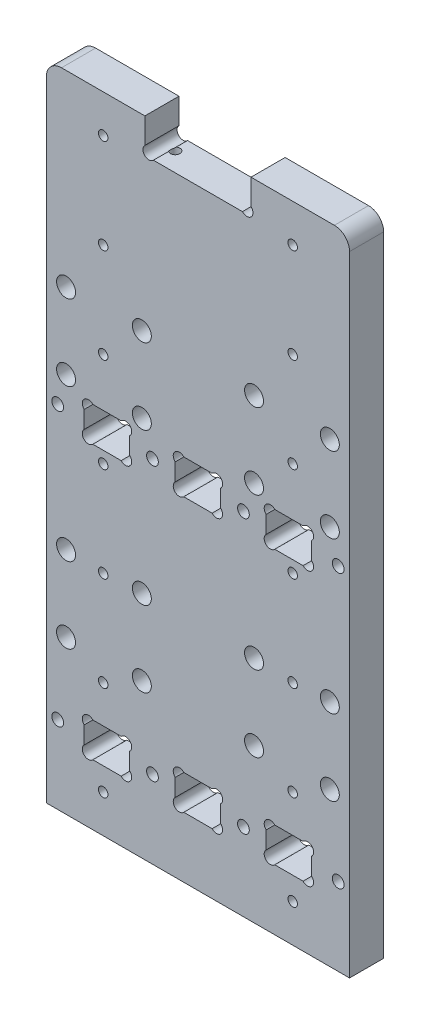
SolidWorks part; units mm, degrees
ref_plane "Front" through (0, 0, 0) normal (0, 0, 1) x (1, 0, 0)
ref_plane "Top" through (0, 0, 0) normal (0, 1, 0) x (1, 0, 0)
ref_plane "Right" through (0, 0, 0) normal (1, 0, 0) x (0, 0, -1)
sketch "Esquisse1" plane through (0, 0, 0) normal (0, 0, 1) x (1, 0, 0)
  line L1 (0, 0) -> (80, 0)
  line L2 (0, 0) -> (0, 170)
  line L3 (0, 170) -> (80, 170)
  line L4 (80, 0) -> (80, 170)
  dimension "D1" = 80
  dimension "D2" = 170
extrude "Boss.-Extru.1" add sketch "Esquisse1" along normal blind 9
sketch "Esquisse2" plane through (0, 0, 9) normal (0, 0, 1) x (1, 0, 0)
  line L0 (40, 0) -> (40, 170) construction
  line L1 (0, 0) -> (80, 0) construction
  line L2 (80, 170) -> (0, 170) construction
  line L3 (15, 10) -> (15, 35) construction
  circle A0 centre (15, 10) radius 1.25
  circle A1 centre (65, 10) radius 1.25
  circle A2 centre (15, 35) radius 1.25
  circle A3 centre (65, 35) radius 1.25
  circle A4 centre (15, 60) radius 1.25
  circle A5 centre (65, 60) radius 1.25
  circle A6 centre (15, 85) radius 1.25
  circle A7 centre (65, 85) radius 1.25
  circle A8 centre (15, 110) radius 1.25
  circle A9 centre (65, 110) radius 1.25
  circle A10 centre (15, 135) radius 1.25
  circle A11 centre (65, 135) radius 1.25
  circle A12 centre (15, 160) radius 1.25
  circle A13 centre (65, 160) radius 1.25
  circle A14 centre (15, 185) radius 1.25
  circle A15 centre (65, 185) radius 1.25
  dimension "D2" = 2.5
  dimension "D1" = 50
  dimension "D3" = 10
  dimension "D5" = 25
  dimension "D4" = 8
extrude "Enlèv. mat.-Extru.1" cut sketch "Esquisse2" against normal through all
sketch "Esquisse4" plane through (0, 0, 9) normal (0, 0, 1) x (1, 0, 0)
  line L0 (40, 170) -> (40, 161) construction
  line L1 (80, 170) -> (0, 170) construction
  line L2 (54, 161) -> (26, 161)
  line L3 (26, 161) -> (26, 170)
  line L4 (26, 170) -> (54, 170)
  line L5 (54, 161) -> (54, 170)
  dimension "D1" = 28
  dimension "D2" = 9
extrude "Enlèv. mat.-Extru.3" cut sketch "Esquisse4" against normal through all
sketch "Esquisse5" plane through (0, 161, 0) normal (0, 1, 0) x (1, 0, 0)
  line L0 (29, 0) -> (29, -4) construction
  line L1 (26, 0) -> (54, 0) construction
  line L2 (40, 0) -> (40, -4.3659) construction
  circle A0 centre (29, -4) radius 1.25
  circle A1 centre (51, -4) radius 1.25
  dimension "D1" = 2.5
  dimension "D2" = 4
  dimension "D3" = 22
extrude "Enlèv. mat.-Extru.4" cut sketch "Esquisse5" against normal blind 10
sketch "Esquisse6" plane through (0, 0, 9) normal (0, 0, 1) x (1, 0, 0)
  line L0 (74.8, 120.5) -> (74.8, 80.5) construction
  line L1 (40, 161) -> (40, 0) construction
  line L2 (26, 161) -> (54, 161) construction
  line L3 (0, 0) -> (80, 0) construction
  line L5 (74.8, 80.5) -> (40, 80.5) construction
  line L6 (5.2, 120.5) -> (5.2, 80.5) construction
  line L7 (74.8, 120.5) -> (64.8, 120.5) construction
  line L8 (64.8, 120.5) -> (64.8, 124.5729) construction
  circle A0 centre (74.8, 120.5) radius 2.5
  circle A1 centre (74.8, 60.5) radius 2.5
  circle A2 centre (74.8, 100.5) radius 2.5
  circle A3 centre (74.8, 40.5) radius 2.5
  circle A4 centre (5.2, 40.5) radius 2.5
  circle A5 centre (5.2, 100.5) radius 2.5
  circle A6 centre (5.2, 60.5) radius 2.5
  circle A7 centre (5.2, 120.5) radius 2.5
  circle A8 centre (54.8, 100.5) radius 2.5
  circle A9 centre (54.8, 120.5) radius 2.5
  circle A10 centre (54.8, 40.5) radius 2.5
  circle A11 centre (54.8, 60.5) radius 2.5
  circle A12 centre (25.2, 60.5) radius 2.5
  circle A13 centre (25.2, 40.5) radius 2.5
  circle A14 centre (25.2, 120.5) radius 2.5
  circle A15 centre (25.2, 100.5) radius 2.5
  dimension "D3" = 5
  dimension "D5" = 20
  dimension "D1" = 34.8
  dimension "D2" = 20
  dimension "D4" = 20
extrude "Enlèv. mat.-Extru.5" cut sketch "Esquisse6" against normal through all
fillet "Congé1" radius 4 2 edges at (80, 170, 4.5) (0, 170, 4.5)
sketch "Esquisse7" plane through (0, 0, 9) normal (0, 0, 1) x (1, 0, 0)
  line L0 (40, 0) -> (40, 161) construction
  line L1 (10, 25.1) -> (22, 25.1)
  line L2 (10, 25.1) -> (10, 16)
  line L3 (10, 16) -> (22, 16)
  line L4 (22, 25.1) -> (22, 16)
  line L5 (0, 0) -> (80, 0) construction
  line L6 (26, 161) -> (54, 161) construction
  line L7 (46, 25.1) -> (34, 25.1)
  line L8 (34, 25.1) -> (34, 16)
  line L9 (34, 16) -> (46, 16)
  line L10 (46, 25.1) -> (46, 16)
  line L11 (58, 25.1) -> (58, 16)
  line L12 (70, 16) -> (58, 16)
  line L13 (70, 25.1) -> (70, 16)
  line L14 (70, 25.1) -> (58, 25.1)
  line L15 (16, 25.1) -> (16, 88.1) construction
  line L16 (16, 56.6) -> (27.6071, 56.6) construction
  line L17 (70, 88.1) -> (58, 88.1)
  line L18 (70, 88.1) -> (70, 97.2)
  line L19 (70, 97.2) -> (58, 97.2)
  line L20 (58, 88.1) -> (58, 97.2)
  line L21 (46, 88.1) -> (46, 97.2)
  line L22 (34, 97.2) -> (46, 97.2)
  line L23 (34, 88.1) -> (34, 97.2)
  line L24 (46, 88.1) -> (34, 88.1)
  line L25 (22, 88.1) -> (22, 97.2)
  line L26 (10, 97.2) -> (22, 97.2)
  line L27 (10, 88.1) -> (10, 97.2)
  line L28 (10, 88.1) -> (22, 88.1)
  point P14 (34, 20.55)
  point P16 (40, 16)
  point P17 (40, 25.1)
  point P37 (40, 88.1)
  point P38 (40, 97.2)
  dimension "D1" = 12
  dimension "D2" = 12
  dimension "D3" = 12
  dimension "D4" = 16
  dimension "D5" = 9.1
  dimension "D6" = 63
extrude "Enlèv. mat.-Extru.6" cut sketch "Esquisse7" against normal through all
sketch "Esquisse8" plane through (0, 0, 9) normal (0, 0, 1) x (1, 0, 0)
  line L0 (10, 16) -> (10, 15.9) construction
  line L1 (10, 16) -> (9.9, 16) construction
  line L2 (10, 16) -> (11.0803, 17.0803) construction
  line L3 (10, 16) -> (22, 16) construction
  line L4 (16, 16) -> (16, 25.1) construction
  line L5 (22, 25.1) -> (10, 25.1) construction
  line L6 (16, 20.55) -> (10, 20.55) construction
  line L7 (10, 25.1) -> (10, 16) construction
  line L8 (10, 25.1) -> (11.0803, 24.0197) construction
  line L9 (10, 25.1) -> (9.9, 25.1) construction
  line L10 (10, 25.1) -> (10, 25.2) construction
  line L11 (22, 25.1) -> (22, 25.2) construction
  line L12 (22, 25.1) -> (22.1, 25.1) construction
  line L13 (22, 25.1) -> (20.9197, 24.0197) construction
  line L14 (22, 16) -> (20.9197, 17.0803) construction
  line L15 (22, 16) -> (22.1, 16) construction
  line L16 (22, 16) -> (22, 15.9) construction
  line L17 (22, 20.55) -> (34, 20.55) construction
  line L18 (22, 16) -> (22, 25.1) construction
  line L19 (34, 25.1) -> (34, 16) construction
  line L20 (40, 16) -> (40, 25.1) construction
  line L21 (34, 16) -> (46, 16) construction
  line L22 (46, 25.1) -> (34, 25.1) construction
  line L23 (28, 20.55) -> (28, 29.7274) construction
  line L24 (34, 16) -> (34, 15.9) construction
  line L25 (34, 16) -> (33.9, 16) construction
  line L26 (34, 16) -> (35.0803, 17.0803) construction
  line L27 (34, 25.1) -> (35.0803, 24.0197) construction
  line L28 (34, 25.1) -> (33.9, 25.1) construction
  line L29 (34, 25.1) -> (34, 25.2) construction
  line L30 (46, 25.1) -> (46, 25.2) construction
  line L31 (46, 25.1) -> (46.1, 25.1) construction
  line L32 (46, 25.1) -> (44.9197, 24.0197) construction
  line L33 (46, 16) -> (44.9197, 17.0803) construction
  line L34 (46, 16) -> (46.1, 16) construction
  line L35 (46, 16) -> (46, 15.9) construction
  line L36 (58, 20.55) -> (46, 20.55) construction
  line L37 (58, 16) -> (58, 15.9) construction
  line L38 (58, 16) -> (57.9, 16) construction
  line L39 (58, 16) -> (59.0803, 17.0803) construction
  line L40 (58, 25.1) -> (59.0803, 24.0197) construction
  line L41 (58, 25.1) -> (57.9, 25.1) construction
  line L42 (58, 25.1) -> (58, 25.2) construction
  line L43 (70, 25.1) -> (70, 25.2) construction
  line L44 (70, 25.1) -> (70.1, 25.1) construction
  line L45 (70, 25.1) -> (68.9197, 24.0197) construction
  line L46 (64, 20.55) -> (70, 20.55) construction
  line L47 (64, 16) -> (64, 25.1) construction
  line L48 (70, 16) -> (68.9197, 17.0803) construction
  line L49 (70, 16) -> (70.1, 16) construction
  line L50 (70, 16) -> (70, 15.9) construction
  line L51 (16, 25.1) -> (16, 88.1) construction
  line L52 (10, 88.1) -> (22, 88.1) construction
  line L53 (16, 56.6) -> (40, 56.6) construction
  line L54 (70, 97.2) -> (70, 97.3) construction
  line L55 (70, 97.2) -> (70.1, 97.2) construction
  line L56 (70, 97.2) -> (68.9197, 96.1197) construction
  line L57 (64, 97.2) -> (64, 88.1) construction
  line L58 (64, 92.65) -> (70, 92.65) construction
  line L59 (70, 88.1) -> (68.9197, 89.1803) construction
  line L60 (70, 88.1) -> (70.1, 88.1) construction
  line L61 (70, 88.1) -> (70, 88) construction
  line L62 (58, 88.1) -> (58, 88) construction
  line L63 (58, 88.1) -> (57.9, 88.1) construction
  line L64 (58, 88.1) -> (59.0803, 89.1803) construction
  line L65 (58, 97.2) -> (59.0803, 96.1197) construction
  line L66 (58, 97.2) -> (57.9, 97.2) construction
  line L67 (58, 97.2) -> (58, 97.3) construction
  line L68 (58, 92.65) -> (46, 92.65) construction
  line L69 (46, 97.2) -> (46, 97.3) construction
  line L70 (46, 97.2) -> (46.1, 97.2) construction
  line L71 (46, 97.2) -> (44.9197, 96.1197) construction
  line L72 (46, 88.1) -> (44.9197, 89.1803) construction
  line L73 (46, 88.1) -> (46.1, 88.1) construction
  line L74 (46, 88.1) -> (46, 88) construction
  line L75 (34, 88.1) -> (34, 88) construction
  line L76 (34, 88.1) -> (33.9, 88.1) construction
  line L77 (34, 88.1) -> (35.0803, 89.1803) construction
  line L78 (34, 97.2) -> (35.0803, 96.1197) construction
  line L79 (34, 97.2) -> (33.9, 97.2) construction
  line L80 (34, 97.2) -> (34, 97.3) construction
  line L81 (40, 97.2) -> (40, 88.1) construction
  line L82 (22, 92.65) -> (34, 92.65) construction
  line L83 (22, 97.2) -> (22, 97.3) construction
  line L84 (22, 97.2) -> (22.1, 97.2) construction
  line L86 (22, 88.1) -> (20.9197, 89.1803) construction
  line L87 (22, 88.1) -> (22.1, 88.1) construction
  line L88 (22, 88.1) -> (22, 88) construction
  line L89 (10, 88.1) -> (10, 88) construction
  line L90 (10, 88.1) -> (9.9, 88.1) construction
  line L91 (10, 88.1) -> (11.0803, 89.1803) construction
  line L92 (16, 92.65) -> (10, 92.65) construction
  line L93 (16, 97.2) -> (16, 88.1) construction
  line L94 (10, 97.2) -> (11.0803, 96.1197) construction
  line L95 (10, 97.2) -> (9.9, 97.2) construction
  line L96 (10, 97.2) -> (10, 97.3) construction
  line L97 (26, 161) -> (26, 160.9) construction
  line L98 (26, 161) -> (25.9, 161) construction
  line L99 (40, 161) -> (40, 171.5112) construction
  line L100 (26, 161) -> (54, 161) construction
  line L101 (54, 161) -> (54.1, 161) construction
  line L102 (54, 161) -> (54, 160.9) construction
  circle A0 centre (11.0803, 17.0803) radius 1.6
  circle A1 centre (11.0803, 24.0197) radius 1.6
  circle A2 centre (20.9197, 24.0197) radius 1.6
  circle A3 centre (20.9197, 17.0803) radius 1.6
  circle A4 centre (35.0803, 17.0803) radius 1.6
  circle A5 centre (35.0803, 24.0197) radius 1.6
  circle A6 centre (44.9197, 24.0197) radius 1.6
  circle A7 centre (44.9197, 17.0803) radius 1.6
  circle A8 centre (59.0803, 17.0803) radius 1.6
  circle A9 centre (59.0803, 24.0197) radius 1.6
  circle A10 centre (68.9197, 24.0197) radius 1.6
  circle A11 centre (68.9197, 17.0803) radius 1.6
  circle A12 centre (68.9197, 96.1197) radius 1.6
  circle A13 centre (68.9197, 89.1803) radius 1.6
  circle A14 centre (59.0803, 89.1803) radius 1.6
  circle A15 centre (59.0803, 96.1197) radius 1.6
  circle A16 centre (44.9197, 96.1197) radius 1.6
  circle A17 centre (44.9197, 89.1803) radius 1.6
  circle A18 centre (35.0803, 89.1803) radius 1.6
  circle A19 centre (35.0803, 96.1197) radius 1.6
  circle A20 centre (20.9197, 96.1197) radius 1.6
  circle A21 centre (20.9197, 89.1803) radius 1.6
  circle A22 centre (11.0803, 89.1803) radius 1.6
  circle A23 centre (11.0803, 96.1197) radius 1.6
  circle A24 centre (27.0803, 162.0803) radius 1.6
  circle A25 centre (52.9197, 162.0803) radius 1.6
  dimension "D1" = 3.2
  dimension "D2" = 45
  dimension "D3" = 0.1
  dimension "D5" = 0.1
extrude "Enlèv. mat.-Extru.7" cut sketch "Esquisse8" against normal through all
sketch "Esquisse9" plane through (0, 0, 9) normal (0, 0, 1) x (1, 0, 0)
  line L0 (40, 97.2) -> (40, 16) construction
  line L1 (43.7395, 97.2) -> (36.2605, 97.2) construction
  line L2 (36.2605, 16) -> (43.7395, 16) construction
  line L3 (40, 56.6) -> (0, 56.6) construction
  line L4 (0, 166) -> (0, 0) construction
  line L5 (34, 92.65) -> (22, 92.65) construction
  line L6 (34, 94.9395) -> (34, 90.3605) construction
  line L7 (22, 90.3605) -> (22, 94.9395) construction
  line L8 (10, 92.65) -> (0, 92.65) construction
  line L9 (10, 94.9395) -> (10, 90.3605) construction
  line L10 (70, 92.65) -> (80, 92.65) construction
  line L11 (70, 20.55) -> (80, 20.55) construction
  line L12 (10, 20.55) -> (0, 20.55) construction
  line L13 (34, 20.55) -> (22, 20.55) construction
  circle A0 centre (3, 92.65) radius 1.55
  circle A1 centre (28, 92.65) radius 1.55
  circle A2 centre (52, 92.65) radius 1.55
  circle A3 centre (77, 92.65) radius 1.55
  circle A4 centre (77, 20.55) radius 1.55
  circle A5 centre (52, 20.55) radius 1.55
  circle A6 centre (28, 20.55) radius 1.55
  circle A7 centre (3, 20.55) radius 1.55
  dimension "D1" = 3
  dimension "D2" = 3.1
extrude "Enlèv. mat.-Extru.8" cut sketch "Esquisse9" against normal through all both and the other way through all
